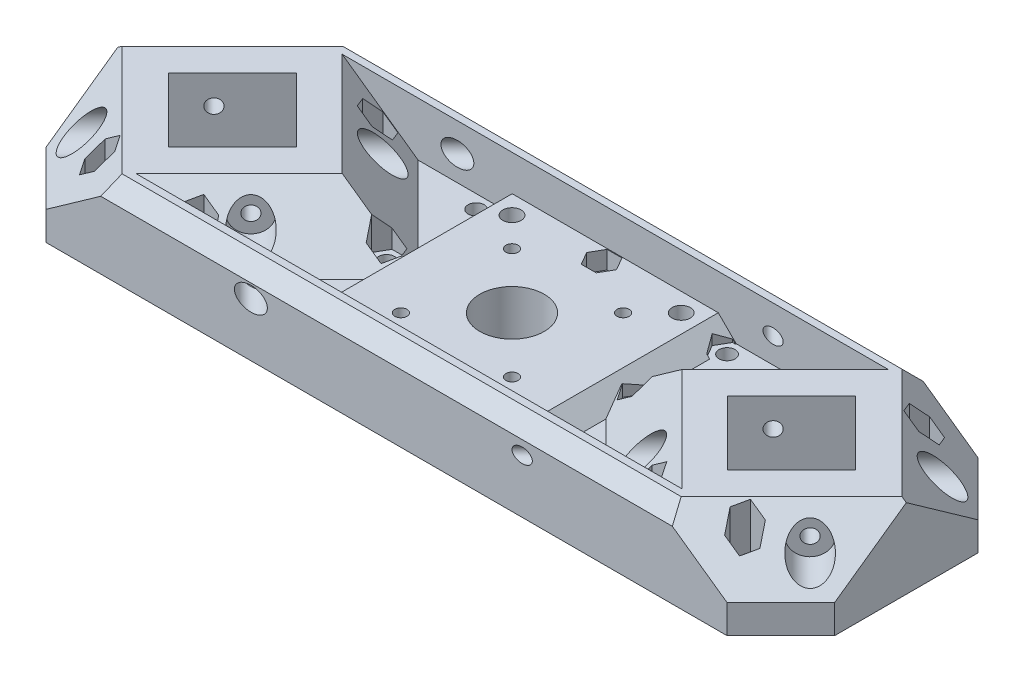
SolidWorks part; units mm, degrees
material "ABS"
ref_plane "Front Plane" through (0, 0, 0) normal (0, 0, 1) x (1, 0, 0)
ref_plane "Top Plane" through (0, 0, 0) normal (0, 1, 0) x (1, 0, 0)
ref_plane "Right Plane" through (0, 0, 0) normal (1, 0, 0) x (0, 0, -1)
sketch "Sketch1" plane through (0, 0, 0) normal (0, 1, 0) x (1, 0, 0)
  line L0 (-110, 0) -> (110, 0) construction
  line L1 (95, 35) -> (-95, 35)
  line L2 (110, 20) -> (110, -20)
  line L3 (95, -35) -> (-95, -35)
  line L4 (-110, 20) -> (-110, -20)
  line L5 (110, 35) -> (-110, -35) construction
  line L6 (110, -35) -> (-110, 35) construction
  line L7 (0, 35) -> (0, -35) construction
  line L8 (-95.8898, 0) -> (-78, 17.8898)
  line L9 (-78, 17.8898) -> (-60.1102, 0)
  line L10 (-60.1102, 0) -> (-78, -17.8898)
  line L11 (-78, -17.8898) -> (-95.8898, 0)
  line L12 (-78, 17.8898) -> (-78, -17.8898) construction
  line L13 (60.1102, 0) -> (78, -17.8898)
  line L14 (78, 17.8898) -> (60.1102, 0)
  line L15 (95.8898, 0) -> (78, 17.8898)
  line L16 (78, -17.8898) -> (95.8898, 0)
  line L17 (-95, 35) -> (-110, 20)
  line L18 (-95, -35) -> (-110, -20)
  line L19 (110, -20) -> (95, -35)
  line L20 (110, 20) -> (95, 35)
  point P0 (0, 0)
  point P8 (-78, 0)
  point P9 (78, 0)
  dimension "D1" = 220
  dimension "D2" = 70
  dimension "D3" = 156
  dimension "D4" = 78
  dimension "D5" = 25.3
extrude "Boss-Extrude1" add sketch "Sketch1" along normal blind 23
chamfer "Chamfer1" distance 15 angle 45 4 edges at (102.5, 23, 27.5) (102.5, 23, -27.5) (-102.5, 23, -27.5) (-102.5, 23, 27.5)
chamfer "Chamfer2" distance 4.2 angle 45 2 edges at (0, 23, -35) (0, 23, 35)
sketch "Sketch3" plane through (0, 23, 0) normal (0, 1, 0) x (1, 0, 0)
  line L0 (-47.3823, 0) -> (-76.1823, 28.8)
  line L1 (-76.1823, 28.8) -> (76.1823, 28.8)
  line L2 (76.1823, 28.8) -> (47.3823, 0)
  line L3 (47.3823, 0) -> (76.1823, -28.8)
  line L4 (76.1823, -28.8) -> (-76.1823, -28.8)
  line L5 (-76.1823, -28.8) -> (-47.3823, 0)
  line L6 (-78, -17.8898) -> (-60.1102, 0) construction
  line L7 (-60.1102, 0) -> (-78, 17.8898) construction
  line L8 (78, 17.8898) -> (60.1102, 0) construction
  line L9 (77.9868, 30.8) -> (-77.9868, 30.8) construction
  line L10 (-77.9868, -30.8) -> (77.9868, -30.8) construction
  line L11 (60.1102, 0) -> (78, -17.8898) construction
  dimension "D1" = 9
  dimension "D2" = 9
  dimension "D3" = 9
  dimension "D4" = 2
  dimension "D5" = 2
  dimension "D6" = 9
extrude "Cut-Extrude1" cut sketch "Sketch3" against normal blind 10
sketch "Sketch4" plane through (0, 13, 0) normal (0, 1, 0) x (1, 0, 0)
  line L1 (-23.6, -23.6) -> (23.6, -23.6) construction
  line L2 (-23.6, -23.6) -> (-23.6, 23.6) construction
  line L3 (-23.6, 23.6) -> (23.6, 23.6) construction
  line L4 (23.6, -23.6) -> (23.6, 23.6) construction
  line L5 (-23.6, -23.6) -> (23.6, 23.6) construction
  line L6 (-23.6, 23.6) -> (23.6, -23.6) construction
  line L7 (-15.5, -15.5) -> (15.5, -15.5) construction
  line L8 (-15.5, -15.5) -> (-15.5, 15.5) construction
  line L9 (-15.5, 15.5) -> (15.5, 15.5) construction
  line L10 (15.5, -15.5) -> (15.5, 15.5) construction
  line L11 (-15.5, -15.5) -> (15.5, 15.5) construction
  line L12 (-15.5, 15.5) -> (15.5, -15.5) construction
  point P0 (0, 0)
  point P5 (0, 0)
  dimension "D1" = 47.2
  dimension "D2" = 47.2
  dimension "D3" = 31
hole_wizard "Ø5.1 (5.1) Diameter Hole1" positions "Sketch5" profile "Sketch6" hole size "Ø5.1" standard "ANSI Metric" end condition through all
sketch "Sketch5" plane through (0, 13, 0) normal (0, 1, 0) x (1, 0, 0)
  point P0 (-23.6, 23.6)
  point P3 (-23.6, -23.6)
  point P6 (23.6, -23.6)
  point P9 (23.6, 23.6)
sketch "Sketch6" plane through (-23.6, 13, -23.6) normal (1, 0, 0) x (0, 0, 1)
  line L0 (0, 0) -> (0, 13)
  line L1 (0, 13) -> (2.55, 13)
  line L2 (2.55, 13) -> (2.55, 0)
  line L5 (2.55, 0) -> (0, 0)
  line L11 (0, -6.35) -> (0, 107.95) construction
  dimension "Thru Hole Dia." = 5.1
  dimension "Thru Hole Depth" = 13
hole_wizard "Ø3.4 (3.4) Diameter Hole1" positions "Sketch7" profile "Sketch8" hole size "Ø3.4" standard "ANSI Metric" end condition through all
sketch "Sketch7" plane through (0, 13, 0) normal (0, 1, 0) x (1, 0, 0)
  point P0 (-15.5, 15.5)
  point P3 (-15.5, -15.5)
  point P6 (15.5, -15.5)
  point P9 (15.5, 15.5)
sketch "Sketch8" plane through (-15.5, 13, -15.5) normal (1, 0, 0) x (0, 0, 1)
  line L0 (0, 0) -> (0, 13)
  line L1 (0, 13) -> (1.7, 13)
  line L2 (1.7, 13) -> (1.7, 0)
  line L5 (1.7, 0) -> (0, 0)
  line L11 (0, -6.35) -> (0, 107.95) construction
  dimension "Thru Hole Dia." = 3.4
  dimension "Thru Hole Depth" = 13
sketch "Sketch9" plane through (0, 13, 0) normal (0, 1, 0) x (1, 0, 0)
  circle A0 centre (0, 0) radius 9
  dimension "D1" = 18
extrude "Cut-Extrude2" cut sketch "Sketch9" against normal through all
sketch "Sketch10" plane through (0, 13, 0) normal (0, 1, 0) x (1, 0, 0)
  line L0 (-28.75, 28.8) -> (-28.75, -28.8)
  line L1 (76.1823, 28.8) -> (-76.1823, 28.8) construction
  line L2 (-76.1823, -28.8) -> (76.1823, -28.8) construction
  line L3 (-28.75, -28.8) -> (-76.1823, -28.8)
  line L4 (-76.1823, -28.8) -> (-47.3823, 0)
  line L5 (-47.3823, 0) -> (-76.1823, 28.8)
  line L6 (-76.1823, 28.8) -> (-28.75, 28.8)
  line L7 (28.75, 28.8) -> (28.75, -28.8)
  line L8 (76.1823, 28.8) -> (-76.1823, 28.8) construction
  line L9 (-76.1823, -28.8) -> (76.1823, -28.8) construction
  line L10 (28.75, -28.8) -> (76.1823, -28.8)
  line L11 (76.1823, -28.8) -> (47.3823, 0)
  line L12 (47.3823, 0) -> (76.1823, 28.8)
  line L13 (76.1823, 28.8) -> (28.75, 28.8)
  dimension "D1" = 57.5
  dimension "D2" = 28.75
extrude "Cut-Extrude3" cut sketch "Sketch10" against normal blind 5
chamfer "Chamfer3" distance 15 angle 45 4 edges at (61.7823, 8, -14.4) (61.7823, 8, 14.4) (-61.7823, 8, -14.4) (-61.7823, 8, 14.4)
chamfer "Chamfer4" distance 5 angle 45 4 edges at (28.75, 8, -15.6905) (28.75, 8, 15.6905) (-28.75, 8, -15.6905) (-28.75, 8, 15.6905)
ref_plane "Plane1" through (0, 8, 0) normal (0, -1, 0) x (-1, 0, 0)
sketch "Sketch11" plane through (0, 8, 0) normal (0, -1, 0) x (-1, 0, 0)
  line L0 (-90, 25) -> (90, 25) construction
  line L1 (-90, -25) -> (90, -25) construction
  line L2 (0, 25) -> (0, -25) construction
  line L3 (-62.5, 25) -> (-62.5, -25) construction
  line L4 (-35, 25) -> (-35, -25) construction
  line L5 (35, 25) -> (35, -25) construction
  line L6 (62.5, 25) -> (62.5, -25) construction
  line L7 (-90, 25) -> (-90, -25) construction
  line L8 (90, 25) -> (90, -25) construction
  line L10 (-94.1569, 25) -> (-92.0785, 21.4)
  line L11 (-92.0785, 21.4) -> (-87.9215, 21.4)
  line L12 (-87.9215, 21.4) -> (-85.8431, 25)
  line L13 (-85.8431, 25) -> (-87.9215, 28.6)
  line L14 (-87.9215, 28.6) -> (-92.0785, 28.6)
  line L15 (-92.0785, 28.6) -> (-94.1569, 25)
  line L16 (-58.3431, 25) -> (-60.4215, 28.6)
  line L17 (-60.4215, 28.6) -> (-64.5785, 28.6)
  line L18 (-64.5785, 28.6) -> (-66.6569, 25)
  line L19 (-66.6569, 25) -> (-64.5785, 21.4)
  line L20 (-64.5785, 21.4) -> (-60.4215, 21.4)
  line L21 (-60.4215, 21.4) -> (-58.3431, 25)
  line L22 (-85.8431, -25) -> (-87.9215, -21.4)
  line L23 (-87.9215, -21.4) -> (-92.0785, -21.4)
  line L24 (-92.0785, -21.4) -> (-94.1569, -25)
  line L25 (-94.1569, -25) -> (-92.0785, -28.6)
  line L26 (-92.0785, -28.6) -> (-87.9215, -28.6)
  line L27 (-87.9215, -28.6) -> (-85.8431, -25)
  line L28 (-58.3431, -25) -> (-60.4215, -21.4)
  line L29 (-60.4215, -21.4) -> (-64.5785, -21.4)
  line L30 (-64.5785, -21.4) -> (-66.6569, -25)
  line L31 (-66.6569, -25) -> (-64.5785, -28.6)
  line L32 (-64.5785, -28.6) -> (-60.4215, -28.6)
  line L33 (-60.4215, -28.6) -> (-58.3431, -25)
  line L34 (-30.8431, -25) -> (-32.9215, -21.4)
  line L35 (-32.9215, -21.4) -> (-37.0785, -21.4)
  line L36 (-37.0785, -21.4) -> (-39.1569, -25)
  line L37 (-39.1569, -25) -> (-37.0785, -28.6)
  line L38 (-37.0785, -28.6) -> (-32.9215, -28.6)
  line L39 (-32.9215, -28.6) -> (-30.8431, -25)
  line L40 (-30.8431, 25) -> (-32.9215, 28.6)
  line L41 (-32.9215, 28.6) -> (-37.0785, 28.6)
  line L42 (-37.0785, 28.6) -> (-39.1569, 25)
  line L43 (-39.1569, 25) -> (-37.0785, 21.4)
  line L44 (-37.0785, 21.4) -> (-32.9215, 21.4)
  line L45 (-32.9215, 21.4) -> (-30.8431, 25)
  line L46 (4.1569, 25) -> (2.0785, 28.6)
  line L47 (2.0785, 28.6) -> (-2.0785, 28.6)
  line L48 (-2.0785, 28.6) -> (-4.1569, 25)
  line L49 (-4.1569, 25) -> (-2.0785, 21.4)
  line L50 (-2.0785, 21.4) -> (2.0785, 21.4)
  line L51 (2.0785, 21.4) -> (4.1569, 25)
  line L52 (4.1569, -25) -> (2.0785, -21.4)
  line L53 (2.0785, -21.4) -> (-2.0785, -21.4)
  line L54 (-2.0785, -21.4) -> (-4.1569, -25)
  line L55 (-4.1569, -25) -> (-2.0785, -28.6)
  line L56 (-2.0785, -28.6) -> (2.0785, -28.6)
  line L57 (2.0785, -28.6) -> (4.1569, -25)
  line L58 (39.1569, -25) -> (37.0785, -21.4)
  line L59 (37.0785, -21.4) -> (32.9215, -21.4)
  line L60 (32.9215, -21.4) -> (30.8431, -25)
  line L61 (30.8431, -25) -> (32.9215, -28.6)
  line L62 (32.9215, -28.6) -> (37.0785, -28.6)
  line L63 (37.0785, -28.6) -> (39.1569, -25)
  line L64 (39.1569, 25) -> (37.0785, 28.6)
  line L65 (37.0785, 28.6) -> (32.9215, 28.6)
  line L66 (32.9215, 28.6) -> (30.8431, 25)
  line L67 (30.8431, 25) -> (32.9215, 21.4)
  line L68 (32.9215, 21.4) -> (37.0785, 21.4)
  line L69 (37.0785, 21.4) -> (39.1569, 25)
  line L70 (66.6569, 25) -> (64.5785, 28.6)
  line L71 (64.5785, 28.6) -> (60.4215, 28.6)
  line L72 (60.4215, 28.6) -> (58.3431, 25)
  line L73 (58.3431, 25) -> (60.4215, 21.4)
  line L74 (60.4215, 21.4) -> (64.5785, 21.4)
  line L75 (64.5785, 21.4) -> (66.6569, 25)
  line L76 (66.6569, -25) -> (64.5785, -21.4)
  line L77 (64.5785, -21.4) -> (60.4215, -21.4)
  line L78 (60.4215, -21.4) -> (58.3431, -25)
  line L79 (58.3431, -25) -> (60.4215, -28.6)
  line L80 (60.4215, -28.6) -> (64.5785, -28.6)
  line L81 (64.5785, -28.6) -> (66.6569, -25)
  line L82 (85.8431, 25) -> (87.9215, 21.4)
  line L83 (87.9215, 21.4) -> (92.0785, 21.4)
  line L84 (92.0785, 21.4) -> (94.1569, 25)
  line L85 (94.1569, 25) -> (92.0785, 28.6)
  line L86 (92.0785, 28.6) -> (87.9215, 28.6)
  line L87 (87.9215, 28.6) -> (85.8431, 25)
  line L88 (85.8431, -25) -> (87.9215, -28.6)
  line L89 (87.9215, -28.6) -> (92.0785, -28.6)
  line L90 (92.0785, -28.6) -> (94.1569, -25)
  line L91 (94.1569, -25) -> (92.0785, -21.4)
  line L92 (92.0785, -21.4) -> (87.9215, -21.4)
  line L93 (87.9215, -21.4) -> (85.8431, -25)
  line L94 (-30.8431, 0) -> (-32.9215, 3.6)
  line L95 (-32.9215, 3.6) -> (-37.0785, 3.6)
  line L96 (-37.0785, 3.6) -> (-39.1569, 0)
  line L97 (-39.1569, 0) -> (-37.0785, -3.6)
  line L98 (-37.0785, -3.6) -> (-32.9215, -3.6)
  line L99 (-32.9215, -3.6) -> (-30.8431, 0)
  line L100 (30.8431, 0) -> (32.9215, -3.6)
  line L101 (32.9215, -3.6) -> (37.0785, -3.6)
  line L102 (37.0785, -3.6) -> (39.1569, 0)
  line L103 (39.1569, 0) -> (37.0785, 3.6)
  line L104 (37.0785, 3.6) -> (32.9215, 3.6)
  line L105 (32.9215, 3.6) -> (30.8431, 0)
  circle A0 centre (-90, 25) radius 3.6 construction
  circle A1 centre (-62.5, 25) radius 3.6 construction
  circle A2 centre (-90, -25) radius 3.6 construction
  circle A3 centre (-62.5, -25) radius 3.6 construction
  circle A4 centre (-35, -25) radius 3.6 construction
  circle A5 centre (-35, 25) radius 3.6 construction
  circle A6 centre (0, 25) radius 3.6 construction
  circle A7 centre (0, -25) radius 3.6 construction
  circle A8 centre (35, -25) radius 3.6 construction
  circle A9 centre (35, 25) radius 3.6 construction
  circle A10 centre (62.5, 25) radius 3.6 construction
  circle A11 centre (62.5, -25) radius 3.6 construction
  circle A12 centre (90, 25) radius 3.6 construction
  circle A13 centre (90, -25) radius 3.6 construction
  circle A14 centre (-35, 0) radius 3.6 construction
  circle A15 centre (35, 0) radius 3.6 construction
  point P7 (-35, 25)
  point P8 (35, 25)
  point P9 (62.5, 25)
  point P10 (62.5, -25)
  point P11 (35, -25)
  point P12 (-35, -25)
  point P13 (-62.5, -25)
  point P14 (-62.5, 25)
  dimension "D9" = 7.2
  dimension "D10" = 7.2
  dimension "D11" = 7.2
  dimension "D12" = 7.2
  dimension "D13" = 7.2
  dimension "D14" = 7.2
  dimension "D15" = 7.2
  dimension "D16" = 7.2
  dimension "D17" = 7.2
  dimension "D18" = 7.2
  dimension "D19" = 7.2
  dimension "D20" = 7.2
  dimension "D21" = 7.2
  dimension "D22" = 7.2
  dimension "D23" = 7.2
  dimension "D24" = 7.2
  dimension "D1" = 25
  dimension "D2" = 50
  dimension "D3" = 35
  dimension "D4" = 27.5
  dimension "D5" = 27.5
  dimension "D6" = 35
  dimension "D7" = 27.5
  dimension "D8" = 27.5
extrude "Cut-Extrude4" cut sketch "Sketch11" against normal through all
hole_wizard "Ø4.5 (4.5) Diameter Hole1" positions "Sketch15" profile "Sketch16" hole size "Ø4.5" standard "ANSI Metric" end condition through all
sketch "Sketch15" plane through (0, 8, 0) normal (0, 1, 0) x (1, 0, 0)
  point P0 (-90, 25)
  point P3 (-90, -25)
  point P6 (-62.5, -25)
  point P9 (-62.5, 25)
  point P12 (-35, 25)
  point P15 (-35, -25)
  point P18 (0, -25)
  point P21 (0, 25)
  point P24 (35, 25)
  point P27 (35, -25)
  point P30 (62.5, 25)
  point P33 (62.5, -25)
  point P36 (90, -25)
  point P39 (90, 25)
  point P43 (-35, 0)
  point P46 (35, 0)
sketch "Sketch16" plane through (-90, 8, -25) normal (1, 0, 0) x (0, 0, 1)
  line L0 (0, 0) -> (0, 8)
  line L1 (0, 8) -> (2.25, 8)
  line L2 (2.25, 8) -> (2.25, 0)
  line L5 (2.25, 0) -> (0, 0)
  line L11 (0, -6.35) -> (0, 107.95) construction
  dimension "Thru Hole Dia." = 4.5
  dimension "Thru Hole Depth" = 8
sketch "Sketch17" plane through (-30.0551, 0, 30.0551) normal (-0.7071, 0, 0.7071) x (0.7071, 0, 0.7071)
  line L0 (-42.5043, 23) -> (-42.5043, 0) construction
  line L1 (-42.5043, 23) -> (-67.8043, 23) construction
  circle A0 centre (-51.5043, 15) radius 2
  dimension "D1" = 9
  dimension "D2" = 8
  dimension "D3" = 4
extrude "Cut-Extrude5" cut sketch "Sketch17" against normal through all
ref_plane "Plane2" through (-22.0648, 0, 22.0648) normal (-0.7071, 0, 0.7071) x (0.7071, 0, 0.7071)
sketch "Sketch18" plane through (-22.0648, 0, 22.0648) normal (-0.7071, 0, 0.7071) x (0.7071, 0, 0.7071)
  circle A0 centre (-51.5043, 15) radius 5
  circle A3 centre (-51.5043, 15) radius 2 construction
  dimension "D1" = 10
extrude "Cut-Extrude6" cut sketch "Sketch18" against normal blind 13
sketch "Sketch19" plane through (-22.0648, 0, 22.0648) normal (0.7071, 0, -0.7071) x (-0.7071, 0, -0.7071)
  circle A0 centre (51.5043, 15) radius 3.25
  dimension "D1" = 6.5
extrude "Cut-Extrude7" cut sketch "Sketch19" along normal through all
mirror "Mirror1" about plane through (0, 0, 0) normal (0, 0, 1) of "Cut-Extrude7", "Cut-Extrude6", "Cut-Extrude5"
ref_plane "Plane3" through (-78, 0, 0) normal (-1, 0, 0) x (0, 0, 1)
mirror "Mirror4" about plane through (-78, 0, 0) normal (-1, 0, 0) of "Cut-Extrude6", "Cut-Extrude5"
mirror "Mirror5" about plane through (0, 0, 0) normal (0, 0, 1) of "Mirror4"
mirror "Mirror6" about plane through (0, 0, 0) normal (1, 0, 0) of "Mirror5", "Cut-Extrude5", "Cut-Extrude6", "Mirror4"
